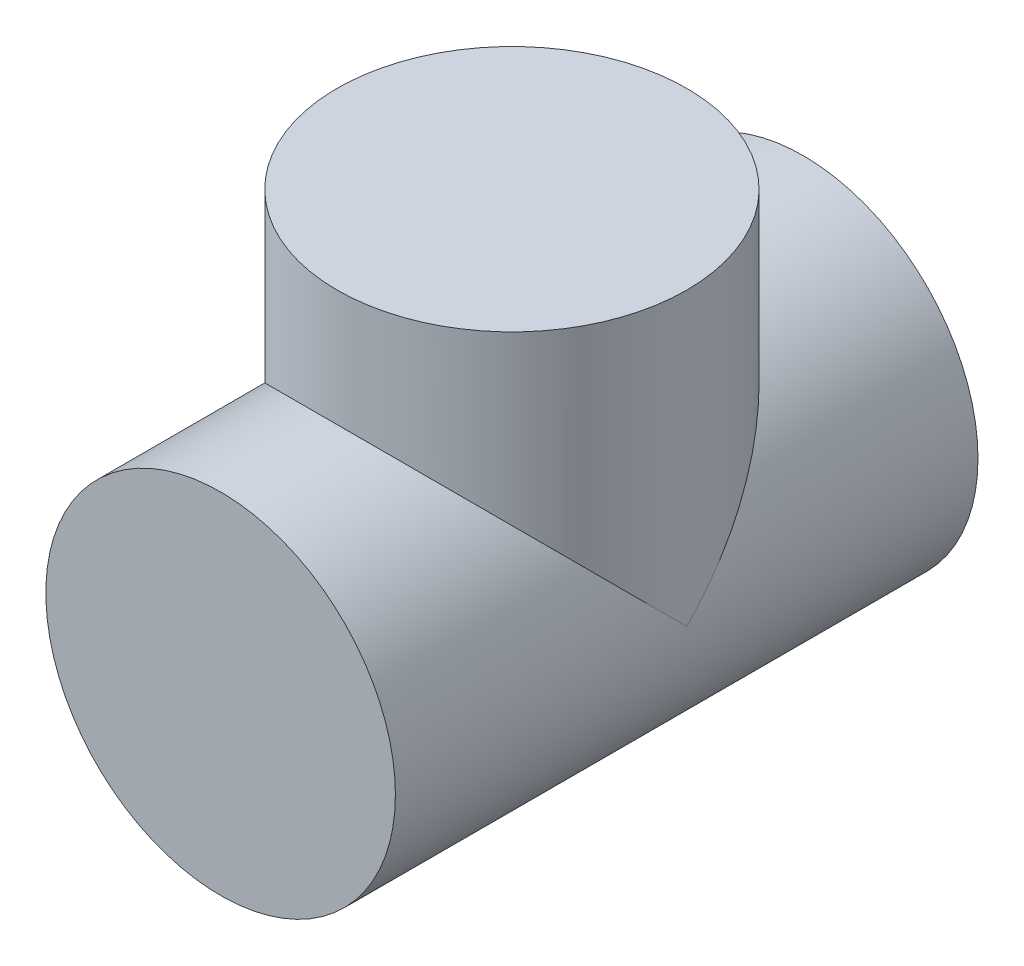
SolidWorks part; units mm, degrees
ref_plane "Front" through (0, 0, 0) normal (0, 0, 1) x (1, 0, 0)
ref_plane "Top" through (0, 0, 0) normal (0, 1, 0) x (1, 0, 0)
ref_plane "Right" through (0, 0, 0) normal (1, 0, 0) x (0, 0, -1)
sketch "Sketch1" plane through (0, 0, 0) normal (0, 0, 1) x (1, 0, 0)
  circle A0 centre (0, 0) radius 7.62
extrude "Boss-Extrude1" add sketch "Sketch1" along normal blind 25.4
sketch "Sketch2" plane through (0, 0, 0) normal (0, 1, 0) x (1, 0, 0)
  line L0 (0, 0) -> (0, -12.7)
  circle A0 centre (0, -12.7) radius 7.62
extrude "Boss-Extrude2" add sketch "Sketch2" along normal blind 12.7 contours A0 region at (-5.2358, 0, 17.9358)
